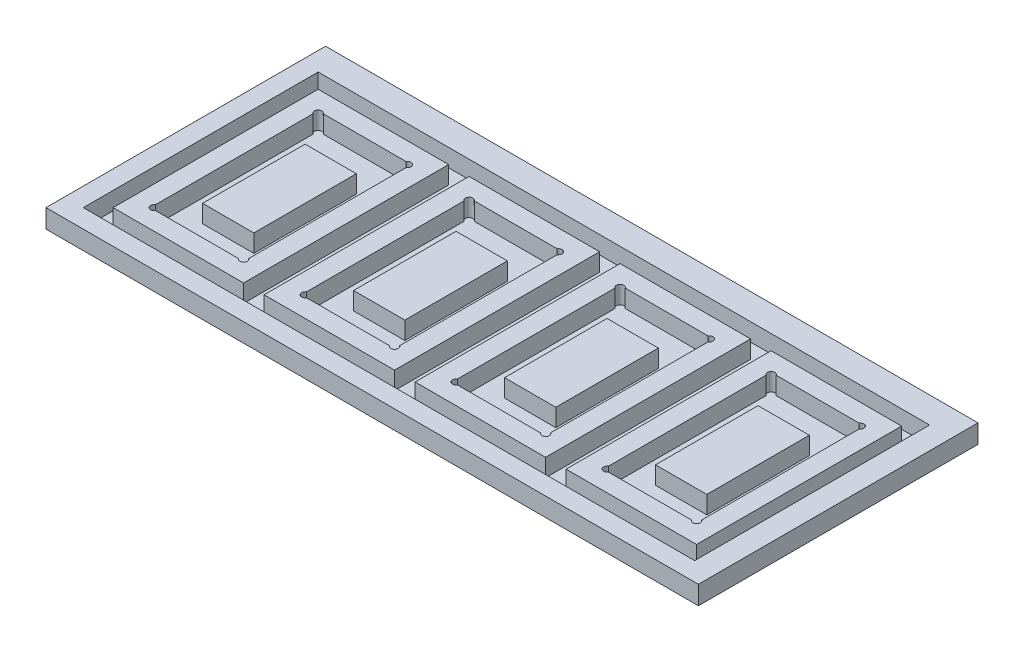
SolidWorks part; units mm, degrees
material "6061 Alloy"
ref_plane "Front Plane" through (0, 0, 0) normal (0, 0, 1) x (1, 0, 0)
ref_plane "Top Plane" through (0, 0, 0) normal (0, 1, 0) x (1, 0, 0)
ref_plane "Right Plane" through (0, 0, 0) normal (1, 0, 0) x (0, 0, -1)
sketch "Sketch1" plane through (0, 0, 0) normal (0, 1, 0) x (1, 0, 0)
  line L1 (-175, -75) -> (175, -75)
  line L2 (-175, -75) -> (-175, 75)
  line L3 (-175, 75) -> (175, 75)
  line L4 (175, -75) -> (175, 75)
  line L5 (-175, -75) -> (175, 75) construction
  line L6 (-175, 75) -> (175, -75) construction
  point P0 (0, 0)
  dimension "D1" = 350
  dimension "D2" = 150
extrude "Boss-Extrude1" add sketch "Sketch1" along normal blind 10
sketch "Sketch2" plane through (0, 10, 0) normal (0, 1, 0) x (1, 0, 0)
  line L0 (98.7562, 43) -> (143.2438, 43)
  line L1 (86, -57) -> (156, -57)
  line L2 (86, -57) -> (86, 53)
  line L3 (86, 53) -> (156, 53)
  line L4 (156, -57) -> (156, 53)
  line L5 (86, -57) -> (156, 53) construction
  line L6 (86, 53) -> (156, -57) construction
  line L7 (146, -44.2438) -> (146, 40.2438)
  line L8 (98.7562, -47) -> (143.2438, -47)
  line L9 (96, -44.2438) -> (96, 40.2438)
  line L10 (96, 43) -> (146, 43) construction
  line L11 (96, -47) -> (96, 43) construction
  line L12 (146, -47) -> (146, 43) construction
  line L13 (96, -47) -> (146, -47) construction
  line L14 (-175, -75) -> (175, -75) construction
  line L15 (108, 24) -> (135.5, 24)
  line L16 (108, 24) -> (108, -31)
  line L17 (108, -31) -> (135.5, -31)
  line L18 (135.5, 24) -> (135.5, -31)
  line L24 (96, -47) -> (96, -44.2438) construction
  line L25 (96, -47) -> (98.7562, -47) construction
  line L26 (143.2438, -47) -> (146, -47) construction
  line L27 (146, -47) -> (146, -44.2438) construction
  line L28 (96, 43) -> (97.0607, 41.9393) construction
  line L29 (146, 43) -> (146, 40.2438) construction
  line L30 (96, 43) -> (98.7562, 43) construction
  line L31 (96, 43) -> (96, 40.2438) construction
  line L32 (146, 43) -> (144.9393, 41.9393) construction
  line L33 (146, -47) -> (144.9393, -45.9393) construction
  line L34 (96, -47) -> (97.0607, -45.9393) construction
  line L35 (5, 53) -> (75, 53)
  line L36 (17.7562, 43) -> (62.2438, 43)
  line L37 (75, -57) -> (75, 53)
  line L38 (65, -44.2438) -> (65, 40.2438)
  line L39 (15, -44.2438) -> (15, 40.2438)
  line L40 (5, -57) -> (5, 53)
  line L41 (5, -57) -> (75, -57)
  line L42 (17.7562, -47) -> (62.2438, -47)
  line L43 (27, 24) -> (27, -31)
  line L44 (27, -31) -> (54.5, -31)
  line L45 (54.5, 24) -> (54.5, -31)
  line L46 (27, 24) -> (54.5, 24)
  line L47 (-76, 53) -> (-6, 53)
  line L48 (-63.2438, 43) -> (-18.7562, 43)
  line L49 (-6, -57) -> (-6, 53)
  line L50 (-16, -44.2438) -> (-16, 40.2438)
  line L51 (-66, -44.2438) -> (-66, 40.2438)
  line L52 (-76, -57) -> (-76, 53)
  line L53 (-76, -57) -> (-6, -57)
  line L54 (-63.2438, -47) -> (-18.7562, -47)
  line L55 (-54, 24) -> (-54, -31)
  line L56 (-54, -31) -> (-26.5, -31)
  line L57 (-26.5, 24) -> (-26.5, -31)
  line L58 (-54, 24) -> (-26.5, 24)
  line L59 (-157, 53) -> (-87, 53)
  line L60 (-144.2438, 43) -> (-99.7562, 43)
  line L61 (-87, -57) -> (-87, 53)
  line L62 (-97, -44.2438) -> (-97, 40.2438)
  line L63 (-147, -44.2438) -> (-147, 40.2438)
  line L64 (-157, -57) -> (-157, 53)
  line L65 (-157, -57) -> (-87, -57)
  line L66 (-144.2438, -47) -> (-99.7562, -47)
  line L67 (-135, 24) -> (-135, -31)
  line L68 (-135, -31) -> (-107.5, -31)
  line L69 (-107.5, 24) -> (-107.5, -31)
  line L70 (-135, 24) -> (-107.5, 24)
  line L73 (-175, 75) -> (-175, -75) construction
  line L79 (-165, 61) -> (163, 61)
  line L80 (-165, 61) -> (-165, -65)
  line L81 (-165, -65) -> (163, -65)
  line L82 (163, 61) -> (163, -65)
  arc A4 (146, 40.2438) -> (143.2438, 43) centre (144.9393, 41.9393) ccw
  arc A5 (98.7562, 43) -> (96, 40.2438) centre (97.0607, 41.9393) ccw
  arc A6 (96, -44.2438) -> (98.7562, -47) centre (97.0607, -45.9393) ccw
  arc A7 (143.2438, -47) -> (146, -44.2438) centre (144.9393, -45.9393) ccw
  arc A8 (65, 40.2438) -> (62.2438, 43) centre (63.9393, 41.9393) ccw
  arc A9 (17.7562, 43) -> (15, 40.2438) centre (16.0607, 41.9393) ccw
  arc A10 (62.2438, -47) -> (65, -44.2438) centre (63.9393, -45.9393) ccw
  arc A11 (15, -44.2438) -> (17.7562, -47) centre (16.0607, -45.9393) ccw
  arc A12 (-16, 40.2438) -> (-18.7562, 43) centre (-17.0607, 41.9393) ccw
  arc A13 (-63.2438, 43) -> (-66, 40.2438) centre (-64.9393, 41.9393) ccw
  arc A14 (-18.7562, -47) -> (-16, -44.2438) centre (-17.0607, -45.9393) ccw
  arc A15 (-66, -44.2438) -> (-63.2438, -47) centre (-64.9393, -45.9393) ccw
  arc A16 (-97, 40.2438) -> (-99.7562, 43) centre (-98.0607, 41.9393) ccw
  arc A17 (-144.2438, 43) -> (-147, 40.2438) centre (-145.9393, 41.9393) ccw
  arc A18 (-99.7562, -47) -> (-97, -44.2438) centre (-98.0607, -45.9393) ccw
  arc A19 (-147, -44.2438) -> (-144.2438, -47) centre (-145.9393, -45.9393) ccw
  dimension "D3" = 4
  dimension "D13" = 45
  dimension "D17" = 4
  dimension "D22" = 4
  dimension "D23" = 4
  dimension "D1" = 110
  dimension "D4" = 55
  dimension "D5" = 27.5
  dimension "D6" = 8
  dimension "D7" = 12
  dimension "D8" = 7
  dimension "D9" = 19
  dimension "D10" = 70
  dimension "D11" = 16
  dimension "D12" = 10.5
  dimension "D14" = 1.5
  dimension "D15" = 45
  dimension "D16" = 1.5
  dimension "D18" = 1.5
  dimension "D19" = 45
  dimension "D20" = 1.5
  dimension "D21" = 45
  dimension "D25" = 11
  dimension "D26" = 10
  dimension "D27" = 8
  dimension "D28" = 8
  dimension "D29" = 10
  dimension "D2" = 10
  dimension "D24" = 4
extrude "Cut-Extrude1" cut sketch "Sketch2" against normal blind 9.5 contours L82 L79 L80 L81 L65 L64 L59 L61 L53 L52 L47 L49 L41 L40 L35 L37 L4 L1 L2 L3 | L63 A19 L66 A18 L62 A16 L60 A17 L67 L70 L69 L68 | L51 A15 L54 A14 L50 A12 L48 A13 L55 L58 L57 L56 | L39 A11 L42 A10 L38 A8 L36 A9 L43 L46 L45 L44 | L8 A7 L7 A4 L0 A5 L9 A6 L15 L18 L17 L16 region at (121, 10, -41.9449) region at (40, 10, -41.9449) region at (-41, 10, -41.9449) region at (-122, 10, -41.9449) region at (-2.4628, 10, 2)
sketch "Sketch3" plane through (0, 10, 0) normal (0, 1, 0) x (1, 0, 0)
  line L0 (175, 75) -> (-175, 75) construction
  line L1 (-133, 75) -> (-110, 75)
  line L2 (-133, 75) -> (-133, -75)
  line L3 (-133, -75) -> (-110, -75)
  line L4 (-110, 75) -> (-110, -75)
  line L5 (-175, -75) -> (175, -75) construction
  line L6 (-122, 43) -> (-122, -47) construction
  line L7 (-144.2438, 43) -> (-99.7562, 43) construction
  line L8 (-144.2438, -47) -> (-99.7562, -47) construction
  line L9 (-144.2438, -47) -> (-99.7562, -47) construction
  dimension "D1" = 12
  dimension "D2" = 11
sketch "Sketch4" plane through (0, 10, 0) normal (0, 1, 0) x (1, 0, 0)
  line L0 (-147, -2) -> (-97, -2) construction
  line L1 (-175, 18) -> (-87, 18)
  line L2 (-175, 18) -> (-175, -22)
  line L3 (-175, -22) -> (-87, -22)
  line L4 (-87, 18) -> (-87, -22)
  line L5 (-147, -44.2438) -> (-147, 40.2438) construction
  line L6 (-97, -44.2438) -> (-97, 40.2438) construction
  line L7 (-175, 75) -> (-175, -75) construction
  line L8 (-87, -57) -> (-87, 53) construction
  dimension "D1" = 20
  dimension "D2" = 20
